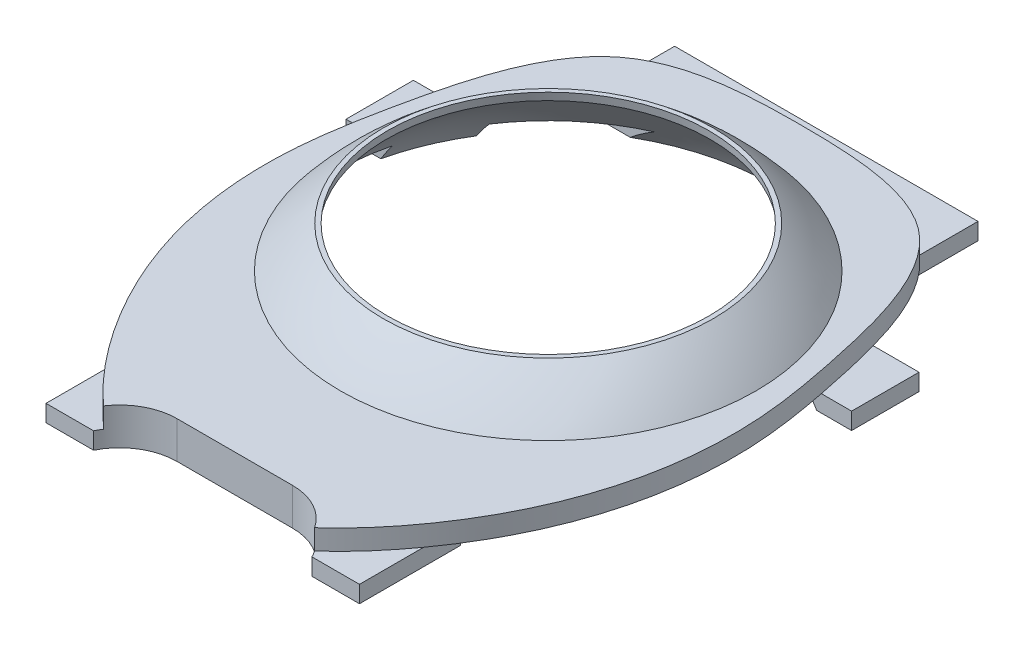
SolidWorks part; units mm, degrees
ref_plane "Front Plane" through (0, 0, 0) normal (0, 0, 1) x (1, 0, 0)
ref_plane "Top Plane" through (0, 0, 0) normal (0, 1, 0) x (1, 0, 0)
ref_plane "Right Plane" through (0, 0, 0) normal (1, 0, 0) x (0, 0, -1)
sketch "Sketch6" plane through (0, 0, 0) normal (0, 1, 0) x (1, 0, 0)
  spline S0 degree 3 poles (-12.7787, 38.4434) (-10.4485, 47.5721) (0, 48.2069) (10.4485, 47.5721) (12.7787, 38.4434) (14.4585, 29.3625) (12.4747, 18.5694) (0, 5.5729) (-12.4747, 18.5694) (-14.4585, 29.3625) (-12.7787, 38.4434) (-10.4485, 47.5721) (0, 48.2069) knots -0.273132 -0.144381 -0.095356 0 0.089263 0.178525 0.273881 0.322906 0.451657 0.589263 0.726868 0.855619 0.904644 1 1.089263 1.178525 1.273881 only from (-9, 46) to (-9, 46)
  point P12 (0, 33)
  dimension "D1" = 11
  dimension "D2" = 9
  dimension "D3" = 11
  dimension "D4" = 9
  dimension "D5" = 13
  dimension "D6" = 9
  dimension "D7" = 13
  dimension "D8" = 38
  dimension "D9" = 2
  dimension "D10" = 11
  dimension "D11" = 22
  dimension "D12" = 13.8
  dimension "D13" = 13.8
  dimension "D14" = 10
  dimension "D15" = 33
extrude "Boss-Extrude1" add sketch "Sketch6" along normal blind 1.2
sketch "Sketch1" plane through (0, 0, 0) normal (0, 1, 0) x (1, 0, 0)
  line L5 (-9.3, 12.5) -> (9.3, 12.5)
  line L6 (-9.3, 12.5) -> (-9.3, 18.5)
  line L7 (-9.3, 18.5) -> (9.3, 18.5)
  line L8 (9.3, 12.5) -> (9.3, 18.5)
  line L9 (-9.3, 12.5) -> (9.3, 18.5) construction
  line L10 (-9.3, 18.5) -> (9.3, 12.5) construction
  line L11 (-15, 40) -> (-10, 40)
  line L12 (-15, 40) -> (-15, 36)
  line L13 (-15, 36) -> (-10, 36)
  line L14 (-10, 40) -> (-10, 36)
  line L15 (-15, 40) -> (-10, 36) construction
  line L16 (-15, 36) -> (-10, 40) construction
  line L17 (-9, 49.5) -> (9, 49.5)
  line L18 (-9, 49.5) -> (-9, 44.5)
  line L19 (-9, 44.5) -> (9, 44.5)
  line L20 (9, 49.5) -> (9, 44.5)
  line L21 (-9, 49.5) -> (9, 44.5) construction
  line L22 (-9, 44.5) -> (9, 49.5) construction
  line L23 (10, 40) -> (15, 40)
  line L24 (10, 40) -> (10, 36)
  line L25 (10, 36) -> (15, 36)
  line L26 (15, 40) -> (15, 36)
  line L27 (10, 40) -> (15, 36) construction
  line L28 (10, 36) -> (15, 40) construction
  point P0 (0, 15.5)
  point P6 (0, 47)
  point P8 (-12.5, 38)
  point P17 (12.5, 38)
  dimension "D2" = 6
  dimension "D3" = 18.6
  dimension "D6" = 5
  dimension "D7" = 18
  dimension "D8" = 5
  dimension "D9" = 4
  dimension "D10" = 10
  dimension "D11" = 10
  dimension "D12" = 5
  dimension "D13" = 4
  dimension "D4" = 9
  dimension "D14" = 15.5
  dimension "D5" = 38
ref_plane "Plane1" through (0, -9, 0) normal (0, 1, 0) x (1, 0, 0)
ref_point "Point1"
ref_plane "Plane2" through (0, 0, -33) normal (0, 0, 1) x (1, 0, 0)
ref_axis "Axis1" through (0, 1.26, -33) along (0, -1, 0)
sketch "Sketch4" plane through (0, 0, -33) normal (0, 0, 1) x (1, 0, 0)
  line L0 (0, 0.8) -> (12.6475, 0.8)
  line L2 (0, 0.8) -> (0, 3.65)
  line L3 (0, 3.65) -> (9.7968, 3.65)
  arc A1 (12.6475, 0.8) -> (9.7968, 3.65) centre (0, -9) ccw
  dimension "D1" = 16
  dimension "D2" = 3.65
  dimension "D3" = 0.8
extrude "Boss-Extrude2" add sketch "Sketch1" against normal blind 1
revolve "Revolve1" add sketch "Sketch4" angle 360 about L2
sketch "Sketch8" plane through (0, 0, -33) normal (0, 0, 1) x (1, 0, 0)
  line L0 (0, -1.5) -> (13.5647, -1.5)
  line L2 (0, -1.5) -> (0, 6.5)
  arc A1 (13.5647, -1.5) -> (0, 6.5) centre (0, -9) ccw
  dimension "D1" = 15.5
  dimension "D2" = 1.5
revolve "Cut-Revolve1" cut sketch "Sketch8" angle 360 about axis through (0, 1.26, -33) along (0, -1, 0)
chamfer "Chamfer1" distance 0.8 angle 45 1 edges at (0, 3.65, -24.043) first distance on face at (0, 3.65, -24.043)
sketch "Sketch11" plane through (0, 0, 0) normal (0, 1, 0) x (1, 0, 0)
  line L0 (-0.1749, -0.4) -> (0.1749, -0.4)
  line L7 (-1.3997, 0.3219) -> (-6.4, 9.3531)
  line L8 (-3.4255, 14.4) -> (3.4255, 14.4)
  line L9 (1.3997, 0.3219) -> (6.4, 9.3531)
  line L10 (-1, -0.4) -> (9.1943, 14.4) construction
  line L11 (-9.1943, 14.4) -> (1, -0.4) construction
  arc A4 (-6.4, 9.3531) -> (-3.4255, 14.4) centre (-3.4255, 11) cw
  arc A5 (3.4255, 14.4) -> (6.4, 9.3531) centre (3.4255, 11) cw
  arc A6 (-0.1749, -0.4) -> (-1.3997, 0.3219) centre (-0.1749, 1) cw
  arc A7 (0.1749, -0.4) -> (1.3997, 0.3219) centre (0.1749, 1) ccw
  point P5 (0, 1.0518)
  point P10 (0, 14.4)
  dimension "D5" = 3.4
  dimension "D8" = 1.4
  dimension "D1" = 0.4
  dimension "D4" = 2
  dimension "D6" = 12.8
  dimension "D7" = 14.8
extrude "Cut-Extrude1" cut sketch "Sketch11" against normal through all both and the other way through all
equation "\"D11@Sketch1\"=\"D10@Sketch1\""
equation "\"D12@Sketch1\"=\"D8@Sketch1\""
equation "\"D13@Sketch1\"=\"D9@Sketch1\""
